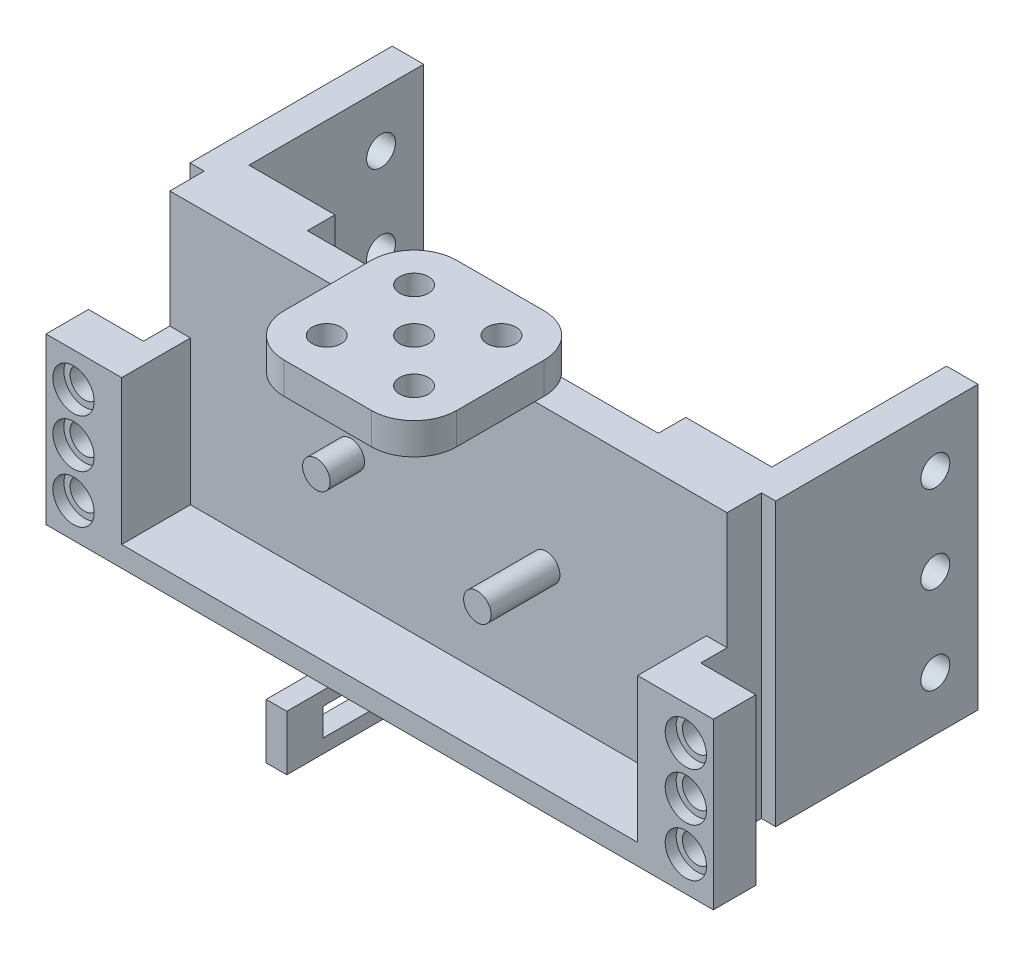
SolidWorks part; units mm, degrees
ref_plane "Front Plane" through (0, 0, 0) normal (0, 0, 1) x (1, 0, 0)
ref_plane "Top Plane" through (0, 0, 0) normal (0, 1, 0) x (1, 0, 0)
ref_plane "Right Plane" through (0, 0, 0) normal (1, 0, 0) x (0, 0, -1)
sketch "Sketch1" plane through (0, 0, 0) normal (0, 0, 1) x (1, 0, 0)
  line L1 (-37.5, -17.5) -> (37.5, -17.5)
  line L2 (-37.5, -17.5) -> (-37.5, 17.5)
  line L3 (-37.5, 17.5) -> (37.5, 17.5)
  line L4 (37.5, -17.5) -> (37.5, 17.5)
  line L5 (-37.5, -17.5) -> (37.5, 17.5) construction
  line L6 (-37.5, 17.5) -> (37.5, -17.5) construction
  point P0 (0, 0)
  dimension "D1" = 75
  dimension "D2" = 35
extrude "Boss-Extrude1" add sketch "Sketch1" along normal blind 5
sketch "Sketch2" plane through (0, 0, 5) normal (0, 0, 1) x (1, 0, 0)
  circle A0 centre (-14.2, 0.5) radius 2
  circle A1 centre (14.2, 0.5) radius 2
  dimension "D4" = 4
  dimension "D5" = 4
extrude "Boss-Extrude2" add sketch "Sketch2" along normal blind 10
sketch "Sketch3" plane through (0, 0, 0) normal (0, 0, -1) x (-1, 0, 0)
  line L1 (-37.5, 17.5) -> (37.5, 17.5)
  line L2 (-37.5, 17.5) -> (-37.5, -17.5)
  line L3 (-37.5, -17.5) -> (37.5, -17.5)
  line L4 (37.5, 17.5) -> (37.5, -17.5)
  line L5 (-37.5, 20.5) -> (-40.5, 20.5)
  line L6 (40.5, -17.5) -> (40.5, -20.5)
  line L8 (-40.5, 20.5) -> (40.5, 20.5)
  line L9 (-40.5, 20.5) -> (-40.5, -20.5)
  line L10 (-40.5, -20.5) -> (40.5, -20.5)
  line L11 (40.5, 20.5) -> (40.5, -20.5)
  line M1 (-37.5, 17.5) -> (-37.5, -17.5)
  line M2 (-37.5, -17.5) -> (37.5, -17.5)
  line M3 (37.5, -17.5) -> (37.5, 17.5)
  line M4 (37.5, 17.5) -> (-37.5, 17.5)
extrude "Boss-Extrude3" add sketch "Sketch3" against normal blind 15 contours L11 L8 L5 L9 L10 L6 M1 M4 M3 M2 region at (-1.5, 19.5921, 0)
sketch "Sketch4" plane through (0, 20.5, 0) normal (0, 1, 0) x (1, 0, 0)
  line L0 (-37.5, -5) -> (-37.5, -12.5)
  line L2 (-37.5, -15) -> (37.5, -15)
  line L4 (37.5, -5) -> (37.5, -12.5)
  line L5 (-37.5, -14) -> (-37.5, -15)
  line L12 (-37.5, -12.5) -> (-37.5, -14)
  line L14 (37.5, -14) -> (37.5, -12.5)
  line L16 (37.5, -15) -> (37.5, -14)
  line L17 (-37.5, -5) -> (37.5, -5)
  dimension "D2" = 1
  dimension "D3" = 1.5
extrude "Cut-Extrude2" cut sketch "Sketch4" against normal blind 10
sketch "Sketch8" plane through (0, 20.5, 0) normal (0, 1, 0) x (1, 0, 0)
  line L0 (0, -5) -> (0, 2.55)
  line L1 (37.5, -5) -> (-37.5, -5) construction
  line L3 (0, -5) -> (0, -15)
  line L4 (0, -15) -> (0, -22.55)
  line L16 (0, 2.55) -> (-12.55, 2.55)
  line L17 (0, 2.55) -> (12.55, 2.55)
  line L18 (0, -22.55) -> (-12.55, -22.55)
  line L19 (0, -22.55) -> (12.55, -22.55)
  line L21 (-12.55, 2.55) -> (12.55, 2.55)
  line L22 (-12.55, 2.55) -> (-12.55, -22.55)
  line L23 (-12.55, -22.55) -> (12.55, -22.55)
  line L24 (12.55, 2.55) -> (12.55, -22.55)
  line M6 (-37.5, -5) -> (37.5, -5)
  line M10 (40.5, 0) -> (-40.5, 0)
  dimension "D1" = 7.55
  dimension "D2" = 10
  dimension "D3" = 7.55
  dimension "D5" = 12.55
extrude "Boss-Extrude6" add sketch "Sketch8" along normal blind 4.57 contours L22 L18 L4 L3 M6 | L24 L3 L4 L19 M6 | L22 L0 M10 M6 | L16 L22 L0 M10 | L24 L17 L0 M10 | L24 L0 M10 M6 region at (-6.275, 20.5, 2.5) region at (6.275, 20.5, 13.775) region at (-6.275, 20.5, 13.775) region at (6.275, 20.5, 2.5) region at (-6.275, 20.5, -1.275) region at (6.275, 20.5, -1.275)
sketch "Sketch9" plane through (0, 25.07, 0) normal (0, 1, 0) x (1, 0, 0)
  circle A0 centre (0, -10) radius 2.1
  circle A1 centre (-6.3498, -3.6502) radius 2.1
  circle A2 centre (6.3498, -3.6502) radius 2.1
  circle A3 centre (6.3498, -16.3498) radius 2.1
  circle A4 centre (-6.3498, -16.3498) radius 2.1
  dimension "D1" = 4.2
  dimension "D2" = 4.2
  dimension "D3" = 4.2
  dimension "D4" = 4.2
  dimension "D5" = 4.2
  dimension "D6" = 8.98
  dimension "D7" = 8.98
  dimension "D8" = 8.98
  dimension "D9" = 8.98
extrude "Cut-Extrude3" cut sketch "Sketch9" against normal blind 4.57
sketch "Sketch14" plane through (0, 20.5, 0) normal (0, 1, 0) x (1, 0, 0)
  line L1 (-37.5, -5) -> (-40.5, -5)
  line L2 (-37.5, -5) -> (-37.5, -15)
  line L3 (-37.5, -15) -> (-40.5, -15)
  line L4 (-40.5, -5) -> (-40.5, -15)
  line L5 (37.5, -5) -> (40.5, -5)
  line L6 (37.5, -5) -> (37.5, -15)
  line L7 (37.5, -15) -> (40.5, -15)
  line L8 (40.5, -5) -> (40.5, -15)
extrude "Cut-Extrude5" cut sketch "Sketch14" against normal blind 17
sketch "Sketch15" plane through (0, 20.5, 0) normal (0, 1, 0) x (1, 0, 0)
  circle A0 centre (-6.3498, -3.6502) radius 2.75
  circle A1 centre (6.3498, -3.6502) radius 2.75
  dimension "D1" = 5.5
  dimension "D2" = 5.5
extrude "Cut-Extrude6" cut sketch "Sketch15" against normal blind 1.5
fillet "Fillet1" radius 1 4 edges at (-8.7458, 19.75, 5) (3.9539, 19.75, 5) (8.7458, 19.75, 5) (-3.9539, 19.75, 5)
sketch "Sketch19" plane through (0, 0, 15) normal (0, 0, 1) x (1, 0, 0)
  circle A0 centre (-14.2, 0.5) radius 2
extrude "Cut-Extrude7" cut sketch "Sketch19" against normal blind 5
sketch "Sketch20" plane through (40.5, 0, 0) normal (1, 0, 0) x (0, 0, -1)
  line L0 (-15, 3.5) -> (-5, 3.5) construction
  line L1 (-15, -20.5) -> (-8.83, -20.5)
  line L2 (-15, -20.5) -> (-15, 3.5)
  line L3 (-15, 3.5) -> (-8.83, 3.5)
  line L4 (-8.83, -20.5) -> (-8.83, 3.5)
  dimension "D1" = 6.17
extrude "Boss-Extrude7" add sketch "Sketch20" along normal blind 8
sketch "Sketch21" plane through (-40.5, 0, 0) normal (-1, 0, 0) x (0, 0, 1)
  line L0 (15, -20.5) -> (0, -20.5) construction
  line L1 (15, 3.5) -> (8.83, 3.5)
  line L2 (15, 3.5) -> (15, -20.5)
  line L3 (15, -20.5) -> (8.83, -20.5)
  line L4 (8.83, 3.5) -> (8.83, -20.5)
  dimension "D1" = 6.17
extrude "Boss-Extrude8" add sketch "Sketch21" along normal blind 8
sketch "Sketch24" plane through (0, 0, 8.83) normal (0, 0, -1) x (-1, 0, 0)
  line L0 (-44.5, 3.5) -> (-44.5, -20.5) construction
  line L1 (-44.5, -8.5) -> (-44.5, 3.5) construction
  line L2 (-44.5, -8.5) -> (-44.5, -20.5) construction
  line L3 (-48.5, 3.5) -> (-40.5, 3.5) construction
  line L6 (-48.5, -20.5) -> (-40.5, -20.5) construction
  line L7 (44.5, 3.5) -> (44.5, -20.5) construction
  line L8 (48.5, 3.5) -> (40.5, 3.5) construction
  line L9 (48.5, -20.5) -> (40.5, -20.5) construction
  circle A0 centre (-44.5, -8.5) radius 2.1
  circle A1 centre (-44.5, -1.5) radius 2.1
  circle A2 centre (-44.5, -15.5) radius 2.1
  circle A3 centre (44.5, -8.5) radius 2.1
  circle A4 centre (44.5, -1.5) radius 2.1
  circle A5 centre (44.5, -15.5) radius 2.1
  dimension "D1" = 4.2
  dimension "D2" = 4.2
  dimension "D3" = 4.2
  dimension "D4" = 4.2
  dimension "D5" = 4.2
  dimension "D6" = 4.2
  dimension "D7" = 7
  dimension "D8" = 7
  dimension "D9" = 7
  dimension "D10" = 7
extrude "Cut-Extrude8" cut sketch "Sketch24" against normal through all
sketch "Sketch25" plane through (0, 0, 15) normal (0, 0, 1) x (1, 0, 0)
  circle A0 centre (-44.5, -1.5) radius 3
  circle A1 centre (-44.5, -8.5) radius 3
  circle A2 centre (-44.5, -15.5) radius 3
  circle A3 centre (44.5, -1.5) radius 3
  circle A4 centre (44.5, -8.5) radius 3
  circle A5 centre (44.5, -15.5) radius 3
  dimension "D1" = 6
  dimension "D2" = 6
  dimension "D3" = 6
  dimension "D4" = 6
  dimension "D5" = 6
  dimension "D6" = 6
extrude "Cut-Extrude9" cut sketch "Sketch25" against normal blind 1.6
sketch "Sketch26" plane through (0, -20.5, 0) normal (0, -1, 0) x (1, 0, 0)
  line L0 (0, 15) -> (-7.5, 15)
  line L1 (48.5, 15) -> (-48.5, 15) construction
  line L2 (-7.5, 15) -> (-7.5, 0)
  line L3 (40.5, 0) -> (-40.5, 0) construction
  line L5 (-7.5, 0) -> (-10.5, 0)
  line L6 (-7.5, 0) -> (-7.5, 21)
  line L7 (-7.5, 21) -> (-10.5, 21)
  line L8 (-10.5, 0) -> (-10.5, 21)
  line M4 (-40.5, 0) -> (40.5, 0)
  line M8 (48.5, 15) -> (-48.5, 15)
  dimension "D1" = 3
  dimension "D2" = 21
  dimension "D3" = 7.5
extrude "Boss-Extrude9" add sketch "Sketch26" along normal blind 8 contours L8 L2 M4 M8 | L8 L6 L7 M8 region at (-9, -20.5, 18) region at (-9, -20.5, 7.5)
sketch "Sketch27" plane through (-10.5, 0, 0) normal (-1, 0, 0) x (0, 0, 1)
  line L0 (21, -28.5) -> (0, -20.5) construction
  line L1 (0, -28.5) -> (21, -20.5) construction
  line L3 (5.25, -26.5) -> (15.75, -26.5)
  line L4 (5.25, -26.5) -> (5.25, -22.5)
  line L5 (5.25, -22.5) -> (15.75, -22.5)
  line L6 (15.75, -26.5) -> (15.75, -22.5)
  line L7 (5.25, -26.5) -> (15.75, -22.5) construction
  line L8 (5.25, -22.5) -> (15.75, -26.5) construction
  point P8 (10.5, -24.5)
  dimension "D1" = 4
extrude "Cut-Extrude10" cut sketch "Sketch27" against normal through all
sketch "Sketch28" plane through (0, -20.5, 0) normal (0, -1, 0) x (1, 0, 0)
  line L0 (-25.5, 0) -> (-42.57, 0)
  line L1 (-10.5, 0) -> (-40.5, 0) construction
  line L2 (-42.57, 0) -> (-42.57, -29.4)
  line L3 (25.5, 0) -> (42.57, 0)
  line L4 (40.5, 0) -> (-7.5, 0) construction
  line L5 (42.57, 0) -> (42.57, -29.4)
  line L6 (-42.57, -29.4) -> (-38, -29.4)
  line L7 (-38, -29.4) -> (-38, -4)
  line L8 (-38, -4) -> (-25.5, -4)
  line L9 (-25.5, -4) -> (-25.5, 0)
  line L10 (42.57, -29.4) -> (38, -29.4)
  line L11 (38, -29.4) -> (38, -4)
  line L12 (38, -4) -> (25.5, -4)
  line L13 (25.5, -4) -> (25.5, 0)
  line L14 (40.5, 8.83) -> (40.5, 0) construction
  line L15 (-40.5, 8.83) -> (-40.5, 0) construction
  dimension "D1" = 29.4
  dimension "D2" = 29.4
  dimension "D3" = 81
  dimension "D4" = 4
  dimension "D5" = 4
  dimension "D6" = 4.57
  dimension "D7" = 4.57
  dimension "D8" = 15
  dimension "D9" = 15
  dimension "D10" = 38
  dimension "D11" = 38
extrude "Boss-Extrude10" add sketch "Sketch28" against normal blind 41
sketch "Sketch30" plane through (-38, 0, 0) normal (1, 0, 0) x (0, 0, -1)
  line L1 (29.4, 0) -> (23.2, 0)
  line L2 (29.4, 20.5) -> (29.4, -20.5) construction
  circle A0 centre (23.2, 0) radius 2.1
  circle A1 centre (23.2, 12.7) radius 2.1
  circle A2 centre (23.2, -12.7) radius 2.1
  dimension "D2" = 4.2
  dimension "D3" = 4.2
  dimension "D4" = 4.2
  dimension "D1" = 6.2
  dimension "D5" = 12.7
  dimension "D6" = 12.7
extrude "Cut-Extrude11" cut sketch "Sketch30" along normal through all and the other way through all contours A2 | A0 | A1 region at (-38, 0, -21.1594) region at (-38, 12.7, -23.2) region at (-38, -12.7, -23.2)
fillet "Fillet2" radius 6.2 4 edges at (-12.55, 22.785, -2.55) (12.55, 22.785, -2.55) (12.55, 22.785, 22.55) (-12.55, 22.785, 22.55)
